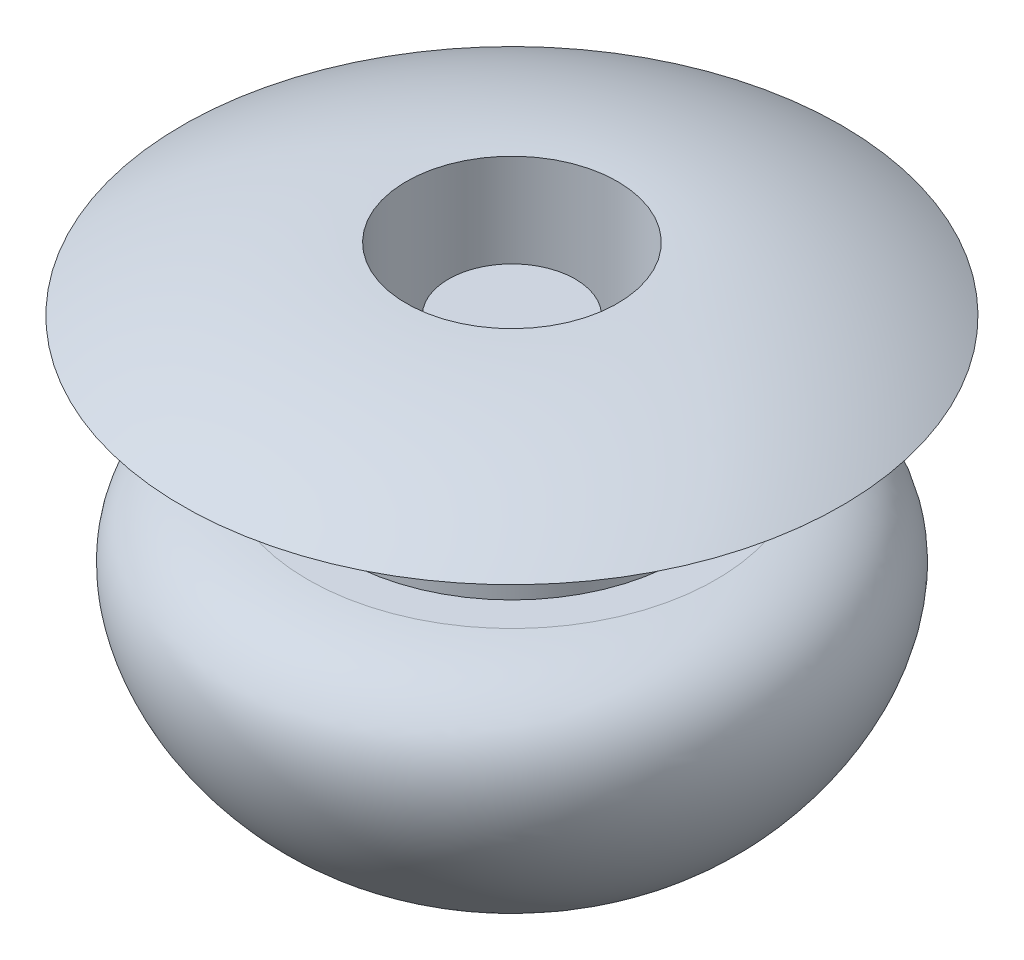
SolidWorks part; units mm, degrees
material "AISI 316 Stal nierdzewna odprężona (SS)"
ref_plane "Płaszczyzna przednia" through (0, 0, 0) normal (0, 0, 1) x (1, 0, 0)
ref_plane "Płaszczyzna górna" through (0, 0, 0) normal (0, 1, 0) x (1, 0, 0)
ref_plane "Płaszczyzna prawa" through (0, 0, 0) normal (1, 0, 0) x (0, 0, -1)
sketch "Szkic1" plane through (0, 0, 0) normal (1, 0, 0) x (0, 0, -1)
  line L1 (0, 0) -> (-0.75, 0)
  line L2 (-0.75, 0) -> (-0.75, -1.7008)
  line L3 (-0.75, -1.7008) -> (-1.25, -1.7008)
  line L4 (-1.25, -1.7008) -> (-1.25, 0.75)
  line L5 (-3.9, 0) -> (-2, 0)
  line L6 (-2, 0) -> (-2, -1.5)
  line L7 (-2, -1.5) -> (-2.4139, -1.5)
  line L8 (0, 0) -> (0, 0.4842) construction
  line L9 (0, -1.7008) -> (0, 0)
  line L10 (0, -1.7008) -> (0, -3.2008)
  line L11 (64.7945, -1.5) -> (68.7945, -1.5) construction
  arc A0 (-1.25, 0.75) -> (-3.9, 0) centre (-1.25, -4.3067) ccw
  ellipse E0 centre (0, -2.4508) end of major axis (-1.75, -2.4508) minor radius 0.75 (-0.956, -3.0789) -> (0, -3.2008) ccw
  spline S0 degree 3 poles (-2.4139, -1.5) (-3.8675, -1.6697) (-3.5289, -3.802) (-1.084, -5.3735) (-0.2718, -3.375) (-0.956, -3.0789) knots 0 0 0 0 0.464993 0.721928 1 1 1 1
  dimension "D1" = 7.8
  dimension "D2" = 2.5
  dimension "D3" = 4
  dimension "D4" = 0.75
  dimension "D5" = 1.5
  dimension "D6" = 1.5
  dimension "D7" = 3.5
  dimension "D8" = 3.1855
  dimension "D9" = 2.5026
  dimension "D10" = 1.9
  dimension "D11" = 1.5789
  dimension "D12" = 0.5792
  dimension "D13" = 4.8278
  dimension "D14" = 3.3858
  dimension "D15" = 2.8395
  dimension "D16" = 1.25
  dimension "D17" = 0.6409
  dimension "D18" = 0.956
revolve "Obrót1" add sketch "Szkic1" angle 360 about L8
